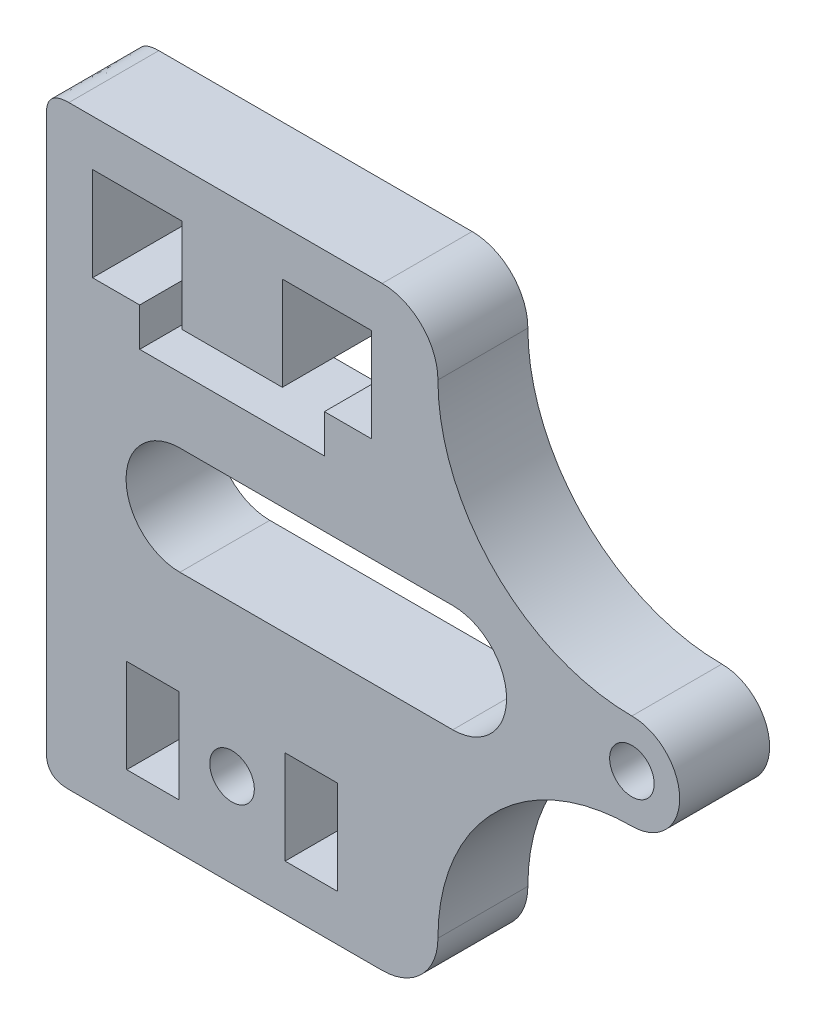
SolidWorks part; units mm, degrees
material "Acrylic (Medium-high impact)"
ref_plane "Front Plane" through (0, 0, 0) normal (0, 0, 1) x (1, 0, 0)
ref_plane "Top Plane" through (0, 0, 0) normal (0, 1, 0) x (1, 0, 0)
ref_plane "Right Plane" through (0, 0, 0) normal (1, 0, 0) x (0, 0, -1)
sketch "Sketch1" plane through (0, 0, 0) normal (0, 0, 1) x (1, 0, 0)
  line L0 (405.5669, 552.3889) -> (405.5669, 554.8889)
  line L1 (396.2885, 554.8889) -> (402.8296, 554.8889)
  line L2 (393.5512, 554.8889) -> (393.5512, 552.3889)
  line L3 (393.5512, 552.3889) -> (405.5669, 552.3889)
  line L4 (390.4885, 560.9889) -> (390.4885, 554.8889)
  line L5 (393.5512, 554.8889) -> (390.4885, 554.8889)
  line L6 (396.2885, 560.9889) -> (390.4885, 560.9889)
  line L7 (396.2885, 554.8889) -> (396.2885, 560.9889)
  line L8 (405.5669, 554.8889) -> (408.6296, 554.8889)
  line L9 (408.6296, 554.8889) -> (408.6296, 560.9889)
  line L10 (402.8296, 560.9889) -> (402.8296, 554.8889)
  line L11 (408.6296, 560.9889) -> (402.8296, 560.9889)
  line L12 (392.709, 534.3889) -> (392.709, 528.2889)
  line L13 (392.709, 528.2889) -> (396.109, 528.2889)
  line L14 (396.109, 534.3889) -> (392.709, 534.3889)
  line L15 (396.109, 528.2889) -> (396.109, 534.3889)
  line L16 (403.009, 528.2889) -> (406.4091, 528.2889)
  line L17 (406.4091, 528.2889) -> (406.4091, 534.3889)
  line L18 (403.009, 534.3889) -> (403.009, 528.2889)
  line L19 (406.4091, 534.3889) -> (403.009, 534.3889)
  line L20 (388.9465, 563.9889) -> (409.3246, 563.9889)
  line L21 (387.4885, 562.5324) -> (387.4885, 526.7454)
  line L22 (388.9465, 525.2889) -> (409.3246, 525.2889)
  line L23 (-605.591, 534.3889) -> (49394.409, 534.3889) construction
  line L24 (396.1657, 548.1389) -> (413.9157, 548.1389)
  line L25 (396.1657, 541.1389) -> (413.9157, 541.1389)
  line L26 (-600.441, 544.6389) -> (49399.559, 544.6389) construction
  line L27 (398.109, 531.3389) -> (396.109, 531.3389) construction
  line L28 (401.009, 531.3389) -> (403.009, 531.3389) construction
  line L29 (399.559, -466.6171) -> (399.559, 49533.3829) construction
  line L30 (425.5694, -455.7473) -> (425.5694, 49544.2527) construction
  line L31 (-608.8734, 554.8889) -> (49391.1266, 554.8889) construction
  line L32 (421.909, 544.6389) -> (421.909, 534.3889) construction
  line L33 (421.909, 544.6389) -> (421.909, 554.8889) construction
  line L34 (412.9514, 560.3621) -> (412.9514, 528.9157) construction
  circle A0 centre (425.5694, 544.6389) radius 1.45
  arc A1 (396.1657, 548.1389) -> (396.1657, 541.1389) centre (396.1657, 544.6389) ccw
  circle A2 centre (399.559, 531.3389) radius 1.45
  arc A3 (412.9514, 528.9157) -> (425.5694, 541.5337) centre (425.5694, 528.9157) cw
  arc A4 (412.9514, 560.3621) -> (425.5694, 547.7441) centre (425.5694, 560.3621) ccw
  arc A5 (425.5694, 547.7441) -> (425.5694, 541.5337) centre (425.5694, 544.6389) cw
  arc A7 (413.9157, 548.1389) -> (413.9157, 541.1389) centre (413.9157, 544.6389) cw
  arc A8 (409.3246, 525.2889) -> (412.9514, 528.9157) centre (409.3246, 528.9157) ccw
  arc A9 (409.3246, 563.9889) -> (412.9514, 560.3621) centre (409.3246, 560.3621) cw
  spline S36 degree 2 poles (387.4885, 562.5324) (387.4083, 563.9889) (388.9465, 563.9889) knots 0 0 0 1 1 1
  spline S37 degree 2 poles (387.4885, 526.7454) (387.4083, 525.2889) (388.9465, 525.2889) knots 0 0 0 1 1 1
  point P26 (399.559, 544.6389)
  point P30 (399.559, 554.8889)
  point P38 (394.409, 534.3889)
  point P40 (412.9514, 544.6389)
  dimension "D5" = 2.9
  dimension "D12" = 6.1
  dimension "D16" = 3.5
  dimension "D2" = 3.4
  dimension "D3" = 5.8
  dimension "D8" = 3
  dimension "D9" = 3
  dimension "D10" = 3
  dimension "D14" = 38.7
  dimension "D15" = 31.4465
  dimension "D17" = 17.75
  dimension "D19" = 13.3924
  dimension "D20" = 22.35
  dimension "D21" = 7
  dimension "Boss_height" = 18
  dimension "Boss_thickness" = 2.5
extrude "Boss-Extrude2" add sketch "Sketch1" along normal blind 5.85
sketch "Sketch2" plane through (0, 0, 0) normal (0, 0, 1) x (1, 0, 0)
  line L0 (-600.441, 531.3389) -> (49399.559, 531.3389) construction
  line L1 (406.4091, 528.2889) -> (406.4091, 534.3889) construction
  circle A0 centre (409.6591, 531.3389) radius 1.25
  point P5 (408.4091, 531.3389)
  dimension "D1" = 2.5
  dimension "D2" = 2
extrude "Cut-Extrude1" cut sketch "Sketch2" along normal blind 1
